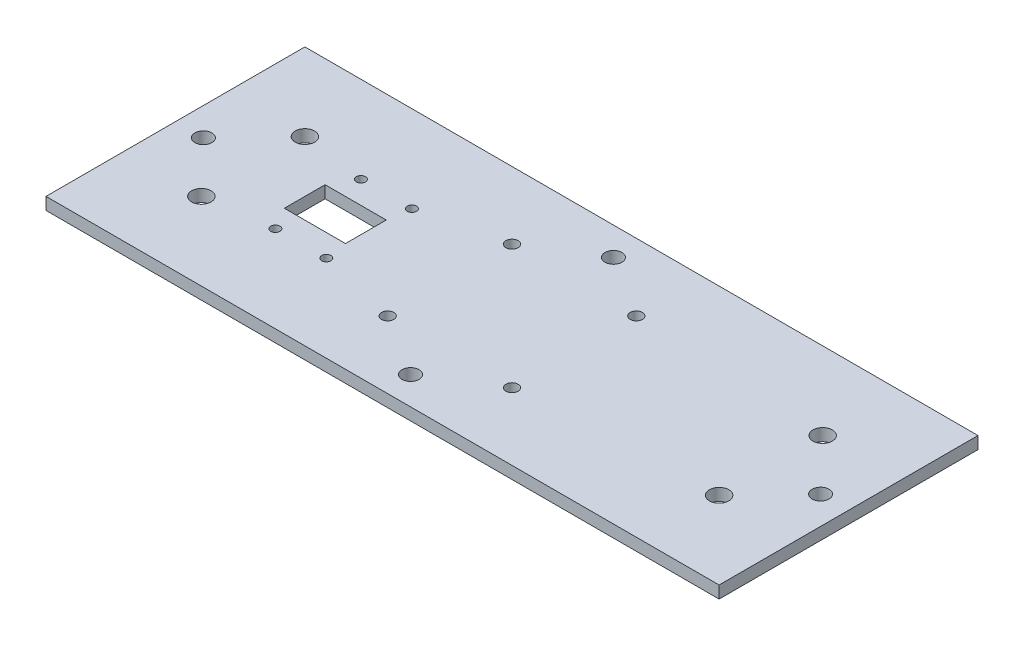
SolidWorks part; units mm, degrees
material "Thornel VCB-20 Carbon Cloth"
ref_plane "Front Plane" through (0, 0, 0) normal (0, 0, 1) x (1, 0, 0)
ref_plane "Top Plane" through (0, 0, 0) normal (0, 1, 0) x (1, 0, 0)
ref_plane "Right Plane" through (0, 0, 0) normal (1, 0, 0) x (0, 0, -1)
sketch "Sketch1" plane through (0, 0, 0) normal (0, 1, 0) x (1, 0, 0)
  line L0 (82.55, -31.75) -> (82.55, 31.75)
  line L1 (82.55, -31.75) -> (-82.55, -31.75)
  line L2 (82.55, 31.75) -> (-82.55, 31.75)
  line L3 (-82.55, -31.75) -> (-82.55, 31.75)
  line L4 (82.55, -31.75) -> (-82.55, 31.75) construction
  line L5 (82.55, 31.75) -> (-82.55, -31.75) construction
  point P1 (0, 0)
  dimension "D1" = 165.1
  dimension "D2" = 63.5
extrude "Boss-Extrude1" add sketch "Sketch1" along normal blind 3
sketch "Sketch6" plane through (0, 0, 0) normal (0, -1, 0) x (1, 0, 0)
  line L0 (-82.55, -31.75) -> (-82.55, 31.75) construction
  line L1 (-50.8, 5.047) -> (-35.8, 5.047)
  line L2 (-50.8, 5.047) -> (-50.8, -4.953)
  line L3 (-50.8, -4.953) -> (-35.8, -4.953)
  line L4 (-35.8, 5.047) -> (-35.8, -4.953)
  line L6 (82.55, -31.75) -> (-82.55, -31.75) construction
  circle A0 centre (-15.25, 15.25) radius 1.5
  circle A1 centre (15.25, 15.25) radius 1.5
  circle A2 centre (-15.25, -15.25) radius 1.5
  circle A3 centre (15.25, -15.25) radius 1.5
  dimension "D5" = 3
  dimension "D6" = 3
  dimension "D7" = 3
  dimension "D8" = 3
  dimension "D1" = 15
  dimension "D2" = 10
  dimension "D3" = 31.75
  dimension "D4" = 26.797
  dimension "D9" = 15.25
  dimension "D10" = 15.25
  dimension "D11" = 15.25
  dimension "D12" = 15.25
  dimension "D13" = 15.25
  dimension "D14" = 15.25
  dimension "D15" = 15.25
  dimension "D16" = 15.25
extrude "Cut-Extrude1" cut sketch "Sketch6" against normal up to next
sketch "Sketch7" plane through (0, 3, 0) normal (0, 1, 0) x (1, 0, 0)
  line L0 (-82.55, 31.75) -> (-82.55, -31.75) construction
  line L1 (82.55, -31.75) -> (82.55, 31.75) construction
  line L2 (-82.55, -31.75) -> (82.55, -31.75) construction
  line L3 (82.55, 31.75) -> (-82.55, 31.75) construction
  circle A0 centre (-77.47, 26.67) radius 1.5
  circle A1 centre (-77.47, -26.67) radius 1.5
  circle A2 centre (77.47, -26.67) radius 1.5
  circle A3 centre (77.47, 26.67) radius 1.5
  dimension "D9" = 3
  dimension "D10" = 3
  dimension "D11" = 3
  dimension "D12" = 3
  dimension "D1" = 5.08
  dimension "D2" = 5.08
  dimension "D3" = 5.08
  dimension "D4" = 5.08
  dimension "D5" = 5.08
  dimension "D6" = 5.08
  dimension "D7" = 5.08
  dimension "D8" = 5.08
sketch "Sketch8" plane through (0, 3, 0) normal (0, 1, 0) x (1, 0, 0)
  line L0 (-82.55, -31.75) -> (82.55, -31.75) construction
  line L1 (-82.55, 31.75) -> (-82.55, -31.75) construction
  line L2 (82.55, -31.75) -> (82.55, 31.75) construction
  line L3 (82.55, 31.75) -> (-82.55, 31.75) construction
  circle A0 centre (-63.5, -12.7) radius 2.3813
  circle A1 centre (-63.5, 12.7) radius 2.3813
  circle A2 centre (63.5, 12.7) radius 2.3813
  circle A3 centre (63.5, -12.7) radius 2.3813
  dimension "D1" = 4.7625
  dimension "D4" = 4.7625
  dimension "D5" = 4.7625
  dimension "D6" = 4.7625
  dimension "D2" = 19.05
  dimension "D3" = 19.05
  dimension "D7" = 19.05
  dimension "D8" = 19.05
  dimension "D9" = 19.05
  dimension "D10" = 19.05
  dimension "D11" = 19.05
  dimension "D12" = 19.05
extrude "Cut-Extrude3" cut sketch "Sketch8" against normal up to next
sketch "Sketch9" plane through (0, 3, 0) normal (0, 1, 0) x (1, 0, 0)
  line L0 (-82.55, 31.75) -> (-82.55, -31.75) construction
  line L1 (82.55, -31.75) -> (82.55, 31.75) construction
  circle A0 centre (-75.692, 0) radius 2.0828
  circle A1 centre (75.692, 0) radius 2.0828
  dimension "D1" = 6.858
  dimension "D2" = 6.858
extrude "Cut-Extrude5" cut sketch "Sketch9" against normal blind 5.08
sketch "Sketch10" plane through (0, 3, 0) normal (0, 1, 0) x (1, 0, 0)
  line L0 (-82.55, -31.75) -> (82.55, -31.75) construction
  line L1 (82.55, 31.75) -> (-82.55, 31.75) construction
  circle A0 centre (0, -24.892) radius 2.0828
  circle A1 centre (0, 24.892) radius 2.0828
  dimension "D1" = 6.858
  dimension "D2" = 6.858
extrude "Cut-Extrude6" cut sketch "Sketch10" against normal blind 5.08 contours A1 | A0
sketch "Sketch11" plane through (0, 3, 0) normal (0, 1, 0) x (1, 0, 0)
  line L1 (-35.05, 10.5) -> (-47.55, 10.5) construction
  line L2 (-35.05, 10.5) -> (-35.05, -10.5) construction
  line L3 (-35.05, -10.5) -> (-47.55, -10.5) construction
  line L4 (-47.55, 10.5) -> (-47.55, -10.5) construction
  line L5 (-35.05, 10.5) -> (-47.55, -10.5) construction
  line L6 (-35.05, -10.5) -> (-47.55, 10.5) construction
  line L7 (-35.8, 4.953) -> (-50.8, 4.953) construction
  circle A0 centre (-47.55, 10.5) radius 1.125
  circle A1 centre (-35.05, 10.5) radius 1.125
  circle A2 centre (-35.05, -10.5) radius 1.125
  circle A3 centre (-47.55, -10.5) radius 1.125
  point P0 (-41.3, 0)
  point P9 (-43.3, 4.953)
  point P11 (-35.4401, 10.5)
  point P13 (-35.3929, -10.5)
  point P15 (-47.1956, -10.5)
  dimension "D4" = 2.25
  dimension "D5" = 2.25
  dimension "D6" = 2.25
  dimension "D7" = 2.25
  dimension "D1" = 12.5
  dimension "D2" = 21
  dimension "D3" = 2
extrude "Cut-Extrude7" cut sketch "Sketch11" against normal blind 41.91
